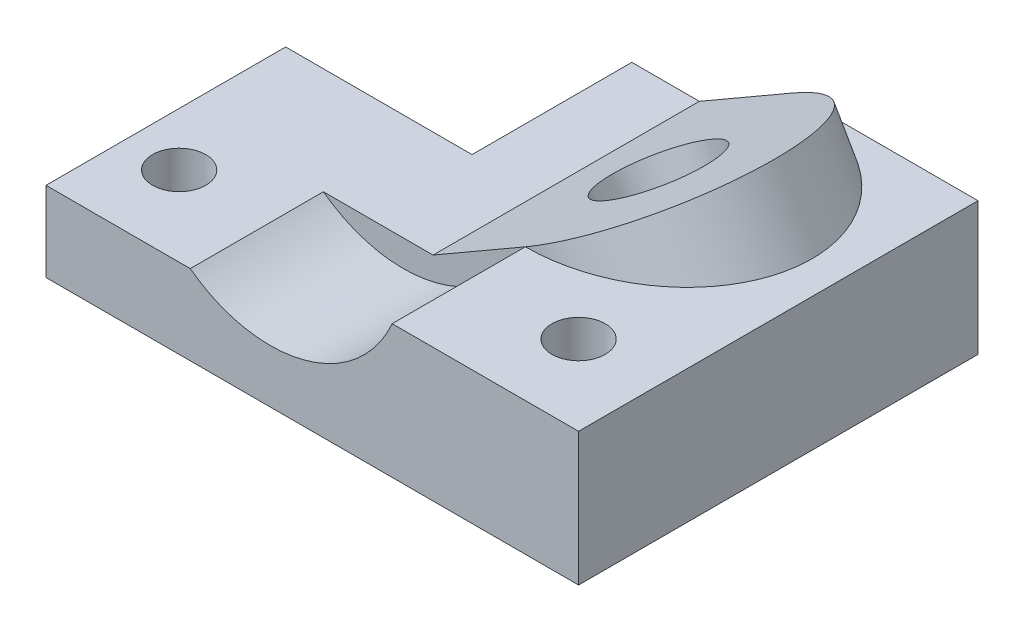
SolidWorks part; units mm, degrees
ref_plane "Ön Düzlem" through (0, 0, 0) normal (0, 0, 1) x (1, 0, 0)
ref_plane "Üst Düzlem" through (0, 0, 0) normal (0, 1, 0) x (1, 0, 0)
ref_plane "Sağ Düzlem" through (0, 0, 0) normal (1, 0, 0) x (0, 0, -1)
sketch "Çizim1" plane through (0, 0, 0) normal (0, 1, 0) x (1, 0, 0)
  line L0 (-65, 75) -> (-65, 45)
  line L1 (0, 0) -> (-100, 0)
  line L2 (0, 0) -> (0, 75)
  line L3 (0, 75) -> (-65, 75)
  line L4 (-100, 0) -> (-100, 45)
  line L5 (-65, 45) -> (-100, 45)
  line L6 (-35, 0) -> (-35, 85.929) construction
  line L7 (-35, 75) -> (-35, 0)
  dimension "D1" = 100
  dimension "D2" = 75
  dimension "D3" = 65
  dimension "D4" = 30
  dimension "D5" = 35
extrude "Yükseklik-Ekstrüzyon1" add sketch "Çizim1" along normal blind 25 contours L3 L7 L1 L2 region at (-17.5, 0, -37.5)
extrude "Yükseklik-Ekstrüzyon2" add sketch "Çizim1<4>" along normal blind 15 contours L7 L3 L0 L5 L4 L1 region at (-63.3824, 0, -31.3235)
sketch "Çizim1<4>" plane through (0, 0, 0) normal (0, 1, 0) x (1, 0, 0) same geometry as "Çizim1"
sketch "Çizim2" plane through (0, 0, 0) normal (0, 0, 1) x (1, 0, 0)
  line L0 (-100, 15) -> (-100, 10) construction
  line L1 (-100, 15) -> (-100, 0) construction
  line L2 (-100, 10) -> (16.1909, 10) construction
  line L4 (-35, 15) -> (-100, 15) construction
  line L5 (-35, 25) -> (-35, 15) construction
  line L6 (-72.9129, 15) -> (-35, 15)
  arc A0 (-35, 25) -> (-72.9129, 15) centre (-57.9129, 35) cw
  line M4 (-35, 25) -> (-35, 15)
  line M5 (-35, 15) -> (-100, 15)
  dimension "D2" = 25
  dimension "D1" = 5
extrude "Kes-Ekstrüzyon1" cut sketch "Çizim2" against normal blind 25 contours A0 L6 region at (-57.9129, 12.9818, 0)
extrude "Yükseklik-Ekstrüzyon3" add sketch "Çizim2<3>" against normal blind 25 contours A0 M4 M5 region at (-37.4079, 18.0164, 0)
sketch "Çizim2<3>" plane through (0, 0, 0) normal (0, 0, 1) x (1, 0, 0) same geometry as "Çizim2"
sketch "Çizim3" plane through (0, 15, 0) normal (0, 1, 0) x (1, 0, 0)
  line L0 (-72.9129, 0) -> (-100, 0) construction
  line L1 (-100, 0) -> (-100, 45) construction
  circle A0 centre (-90, 15) radius 5
  dimension "D1" = 10
  dimension "D2" = 15
  dimension "D3" = 10
extrude "Kes-Ekstrüzyon2" cut sketch "Çizim3" against normal blind 25
sketch "Çizim4" plane through (0, 25, 0) normal (0, 1, 0) x (1, 0, 0)
  line L0 (0, 0) -> (-35, 0) construction
  line L1 (0, 0) -> (0, 75) construction
  circle A0 centre (-15, 15) radius 5
  dimension "D1" = 10
  dimension "D2" = 15
  dimension "D3" = 15
extrude "Kes-Ekstrüzyon3" cut sketch "Çizim4" against normal through all
ref_plane "Düzlem1" through (0, 0, -75) normal (0, 0, 1) x (1, 0, 0)
sketch "Çizim5" plane through (0, 0, -75) normal (0, 0, 1) x (1, 0, 0)
  line L0 (-35, 25) -> (-52.3205, 15)
  line L1 (-35, 15) -> (-65, 15) construction
  line L2 (-52.3205, 15) -> (-35, 15)
  line L3 (-35, 15) -> (-35, 25)
  dimension "D1" = 30
extrude "Yükseklik-Ekstrüzyon4" add sketch "Çizim5" along normal blind 50
sketch "Çizim6" plane through (-19.5753, 33.9054, 0) normal (-0.5, 0.866, 0) x (0.866, 0.5, 0)
  line L0 (-17.8109, 75) -> (-17.8109, 25) construction
  line L5 (-17.8109, 75) -> (-37.8109, 75)
  line L6 (-37.8109, 75) -> (-37.8109, 25)
  line L7 (-37.8109, 25) -> (-17.8109, 25)
  line L8 (-17.8109, 25) -> (-17.8109, 75)
  line L12 (-17.8109, 25) -> (-17.8109, 75)
  arc A0 (-17.8109, 25) -> (-17.8109, 75) centre (-17.8109, 50) ccw
  dimension "D1" = 0
extrude "Yükseklik-Ekstrüzyon5" add sketch "Çizim6" against normal up to surface up to face at (-15, 25, -10)
sketch "Çizim7" plane through (-19.5753, 33.9054, 0) normal (-0.5, 0.866, 0) x (0.866, 0.5, 0)
  circle A0 centre (-17.8109, 50) radius 10
  dimension "D1" = 20
extrude "Kes-Ekstrüzyon4" cut sketch "Çizim7" against normal through all
